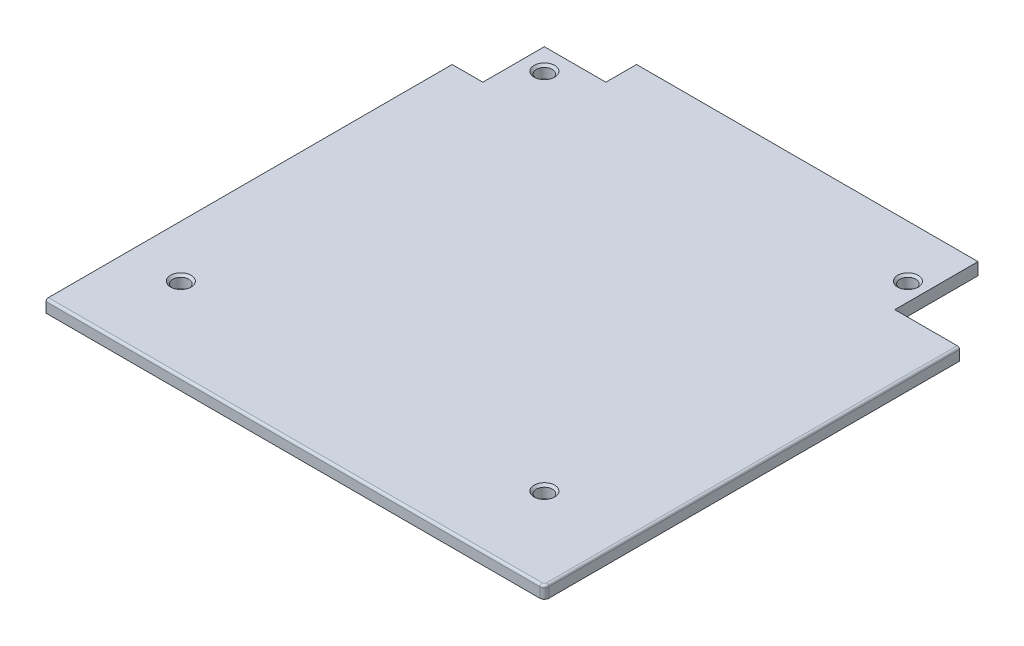
SolidWorks part; units mm, degrees
ref_plane "Front Plane" through (0, 0, 0) normal (0, 0, 1) x (1, 0, 0)
ref_plane "Top Plane" through (0, 0, 0) normal (0, 1, 0) x (1, 0, 0)
ref_plane "Right Plane" through (0, 0, 0) normal (1, 0, 0) x (0, 0, -1)
sketch "Sketch1" plane through (0, 0, 0) normal (0, 1, 0) x (1, 0, 0)
  line L0 (0, -76.2) -> (0, 76.2) construction
  line L1 (-66.25, -66.25) -> (66.25, -66.25) construction
  line L2 (-66.25, -66.25) -> (-66.25, 66.25) construction
  line L3 (-66.25, 66.25) -> (66.25, 66.25) construction
  line L4 (66.25, -66.25) -> (66.25, 66.25) construction
  line L5 (-66.25, -66.25) -> (66.25, 66.25) construction
  line L6 (-66.25, 66.25) -> (66.25, -66.25) construction
  line L11 (-66.2, 46.15) -> (-76.2, 46.15)
  line L12 (-46.15, 66.2) -> (-46.15, 76.2)
  line L15 (-46.15, 76.2) -> (65.15, 76.2)
  line L16 (86.25, 49.08) -> (86.25, -84.75)
  line L17 (84.75, -86.25) -> (-76.2, -86.25)
  line L18 (-76.2, -86.25) -> (-76.2, 46.15)
  line L19 (-66.2, 46.15) -> (-66.2, 66.2)
  line L20 (-66.2, 66.2) -> (-46.15, 66.2)
  line L21 (65.15, 76.2) -> (65.15, 49.08)
  line L22 (65.15, 49.08) -> (86.25, 49.08)
  circle A0 centre (-59.25, 59.25) radius 1.85
  circle A1 centre (-59.25, -59.25) radius 1.85
  circle A3 centre (59.25, -59.25) radius 1.85
  circle A4 centre (59.25, 59.25) radius 1.85
  circle A5 centre (-59.25, 59.25) radius 2.6
  circle A6 centre (59.25, 59.25) radius 2.6
  circle A7 centre (59.25, -59.25) radius 2.6
  circle A8 centre (-59.25, -59.25) radius 2.6
  arc A9 (86.25, -84.75) -> (84.75, -86.25) centre (84.75, -84.75) cw
  point P0 (0, 0)
  point P16 (0, 0)
  dimension "D2" = 3.7
  dimension "D3" = 7
  dimension "D7" = 20
  dimension "D9" = 5.2
  dimension "D10" = 1.5
  dimension "D1" = 132.5
  dimension "D4" = 9.95
  dimension "D5" = 20
  dimension "D6" = 20.1
  dimension "D8" = 9.95
  dimension "D11" = 10
  dimension "D12" = 27.12
  dimension "D13" = 21.1
extrude "Boss-Extrude1" add sketch "Sketch1" along normal mid plane 4 contours L18 L17 L16 L15 L12 L11 A8 A7 A6 A5 | A5 A0 | A6 A4 | A7 A3 | A8 A1 region at (4.8317, 0, 7.9691) region at (-61.7765, 0, -59.25) region at (56.7235, 0, -59.25) region at (56.7235, 0, 59.25) region at (-61.7765, 0, 59.25)
chamfer "Chamfer2" distance 1.5 angle 45 4 edges at (-59.25, 2, -57.4) (59.25, 2, -57.4) (-59.25, 2, 61.1) (59.25, 2, 61.1)
extrude "Cut-Extrude2" cut sketch "Sketch1<4>" along normal up to surface (2 mm away) from surface contours A5 A0 | A8 A1 | A7 A3 | A6 A4 region at (-61.7765, 0, -59.25) region at (56.7235, 0, -59.25) region at (56.7235, 0, 59.25) region at (-61.7765, 0, 59.25) up to face at (59.25, 2, -55.9) starting at face at (0.9782, -2, -19.7908)
sketch "Sketch1<4>" plane through (0, 0, 0) normal (0, 1, 0) x (1, 0, 0) same geometry as "Sketch1"
fillet "Fillet1" radius 0.75 3 edges at (86.25, 2, 17.835) (85.8107, 2, 85.8107) (4.275, 2, 86.25)
